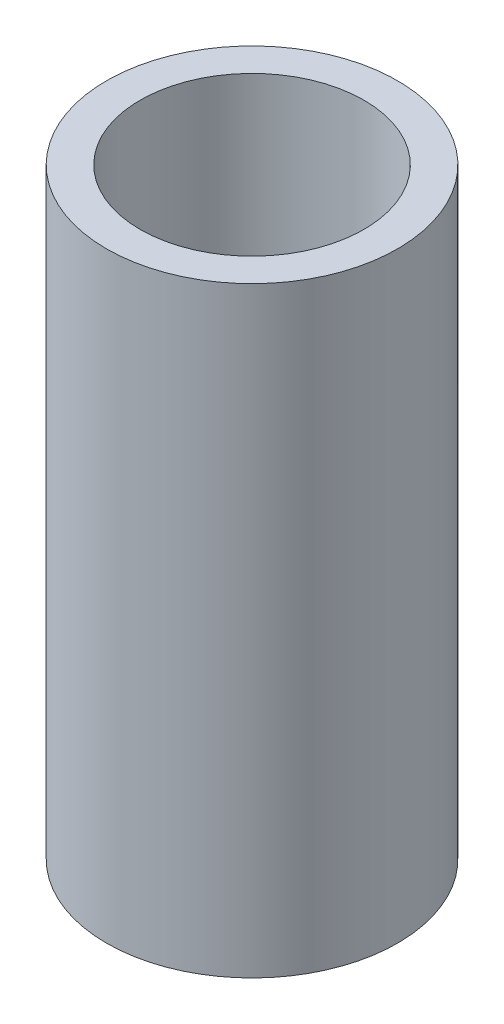
SolidWorks part; units mm, degrees
ref_plane "Front Plane" through (0, 0, 0) normal (0, 0, 1) x (1, 0, 0)
ref_plane "Top Plane" through (0, 0, 0) normal (0, 1, 0) x (1, 0, 0)
ref_plane "Right Plane" through (0, 0, 0) normal (1, 0, 0) x (0, 0, -1)
sketch "Sketch1" plane through (0, 0, 0) normal (0, 1, 0) x (1, 0, 0)
  circle A0 centre (0, 0) radius 15
  dimension "SLEEVE_OD" = 30
extrude "Boss-Extrude1" add sketch "Sketch1" along normal blind 61.9593
sketch "Sketch2" plane through (0, 0, 0) normal (0, 1, 0) x (1, 0, 0)
  circle A0 centre (0, 0) radius 11.5358
  dimension "BORE_D" = 23.0715
extrude "Cut-Extrude1" cut sketch "Sketch2" along normal through all
chamfer "Chamfer1" distance 2.0106 angle 41.908 rebuild error yes
